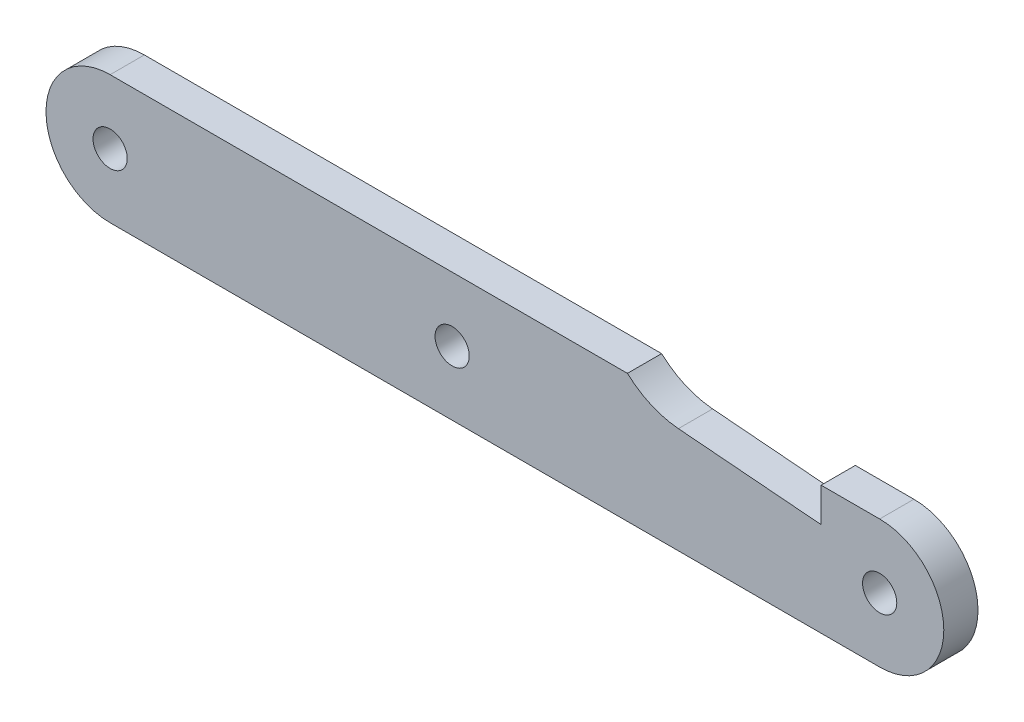
SolidWorks part; units mm, degrees
material "Pine"
ref_plane "Front Plane" through (0, 0, 0) normal (0, 0, 1) x (1, 0, 0)
ref_plane "Top Plane" through (0, 0, 0) normal (0, 1, 0) x (1, 0, 0)
ref_plane "Right Plane" through (0, 0, 0) normal (1, 0, 0) x (0, 0, -1)
sketch "Sketch1" plane through (0, 0, 0) normal (0, 0, 1) x (1, 0, 0)
  line L0 (0, 0) -> (90, 0) construction
  line L1 (0, 7.5) -> (60.5, 7.5)
  line L2 (0, -7.5) -> (90, -7.5)
  line L3 (83.1517, 3.5) -> (83.1517, 7.5)
  line L4 (83.1517, 7.5) -> (90, 7.5)
  line L5 (83.1517, 3.5) -> (62.5958, 5.2)
  line L6 (62.5958, 5.2) -> (60.5, 7.5)
  arc A0 (0, 7.5) -> (0, -7.5) centre (0, 0) ccw
  arc A1 (90, -7.5) -> (90, 7.5) centre (90, 0) ccw
  circle A2 centre (0, 0) radius 2
  circle A3 centre (90, 0) radius 2
  circle A4 centre (40, 0) radius 2
  point P3 (45, 0)
  dimension "D1" = 4
  dimension "D4" = 50
  dimension "D2" = 4
  dimension "D3" = 90
  dimension "D5" = 7.5
  dimension "D6" = 2.3
  dimension "D7" = 6.8483
  dimension "D8" = 2.0958
  dimension "D9" = 20.5559
extrude "Boss-Extrude1" add sketch "Sketch1" along normal blind 4 contours L2 A1 L1 A0 A2 A4 A3 region at (43.7041, -0.2795, 0)
fillet "Fillet1" radius 10 1 edges at (62.5958, 5.2, 2)
